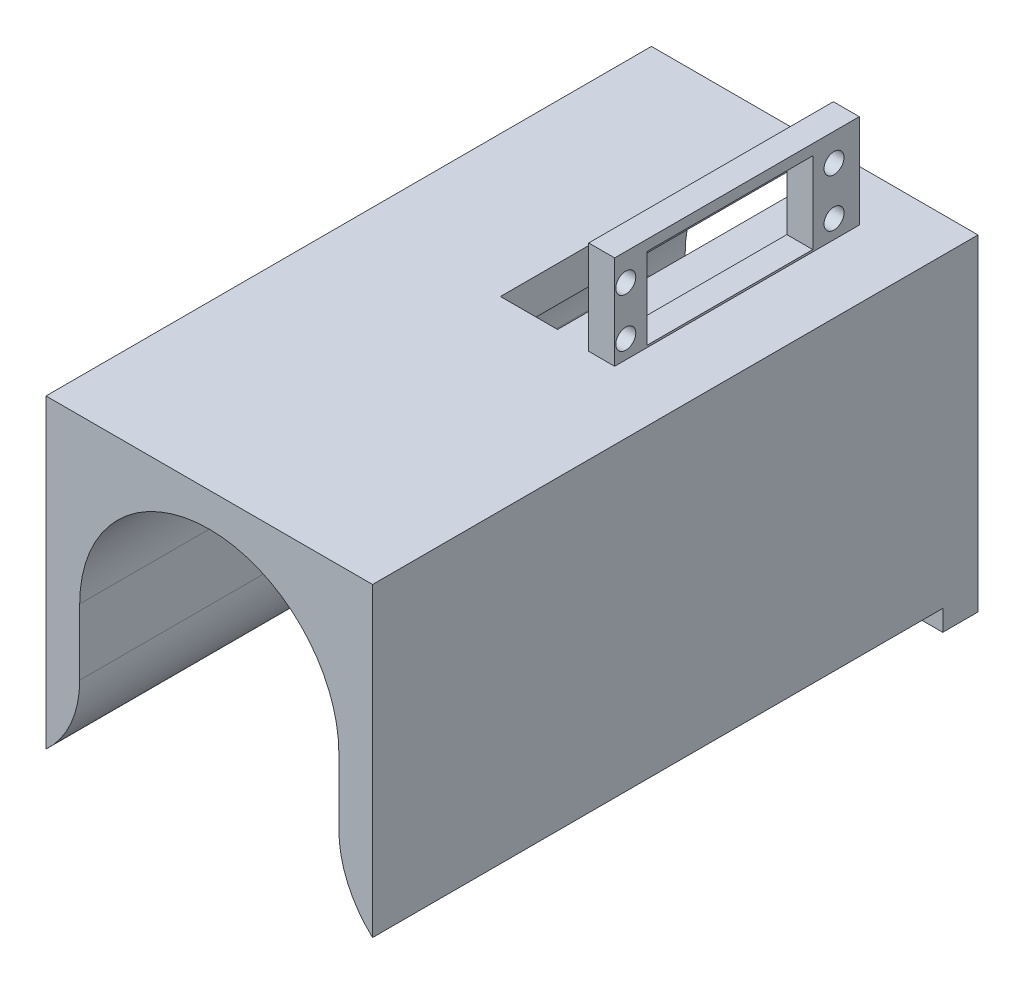
SolidWorks part; units mm, degrees
ref_plane "Front Plane" through (0, 0, 0) normal (0, 0, 1) x (1, 0, 0)
ref_plane "Top Plane" through (0, 0, 0) normal (0, 1, 0) x (1, 0, 0)
ref_plane "Right Plane" through (0, 0, 0) normal (1, 0, 0) x (0, 0, -1)
sketch "Sketch1" plane through (0, 0, 0) normal (0, 0, 1) x (1, 0, 0)
  line L5 (-34.925, -34.925) -> (34.925, 34.925) construction
  line L6 (-34.925, 34.925) -> (34.925, -34.925) construction
  line L7 (-40.005, -40.005) -> (40.005, -40.005)
  line L8 (-40.005, -40.005) -> (-40.005, 40.005)
  line L9 (-40.005, 40.005) -> (40.005, 40.005)
  line L10 (40.005, -40.005) -> (40.005, 40.005)
  line L11 (-40.005, -40.005) -> (40.005, 40.005) construction
  line L12 (-40.005, 40.005) -> (40.005, -40.005) construction
  point P0 (0, 0)
  point P6 (0, 0)
extrude "Boss-Extrude1" add sketch "Sketch1" along normal blind 2.54
sketch "Sketch2" plane through (0, 0, 2.54) normal (0, 0, 1) x (1, 0, 0)
  line L1 (-40.005, 40.005) -> (40.005, 40.005)
  line L2 (-40.005, 40.005) -> (-40.005, -40.005)
  line L3 (-40.005, -40.005) -> (40.005, -40.005)
  line L4 (40.005, 40.005) -> (40.005, -40.005)
  line L5 (-34.925, -34.925) -> (34.925, -34.925)
  line L6 (-34.925, -34.925) -> (-34.925, 34.925)
  line L7 (-34.925, 34.925) -> (34.925, 34.925)
  line L8 (34.925, -34.925) -> (34.925, 34.925)
  line L9 (-34.925, -34.925) -> (34.925, 34.925) construction
  line L10 (-34.925, 34.925) -> (34.925, -34.925) construction
  point P6 (0, 0)
  dimension "D1" = 5.08
  dimension "D2" = 5.08
extrude "Boss-Extrude2" add sketch "Sketch2" along normal blind 145.796
sketch "Sketch3" plane through (0, 0, 0) normal (0, 0, -1) x (-1, 0, 0)
  circle A0 centre (0, 0) radius 31.75
  dimension "D1" = 63.5
extrude "Cut-Extrude1" cut sketch "Sketch3" against normal blind 69.85
sketch "Sketch5" plane through (0, -40.005, 0) normal (0, -1, 0) x (1, 0, 0)
  line L1 (-40.005, 148.336) -> (40.005, 148.336)
  line L2 (-40.005, 148.336) -> (-40.005, 8.636)
  line L3 (-40.005, 8.636) -> (40.005, 8.636)
  line L4 (40.005, 148.336) -> (40.005, 8.636)
  line L5 (-40.005, 148.336) -> (40.005, 8.636) construction
  line L6 (40.005, 148.336) -> (-40.005, 8.636) construction
  point P5 (0, 78.486)
  dimension "D1" = 139.7
extrude "Cut-Extrude3" cut sketch "Sketch5" against normal blind 5.08 contours L3 L1 | L1 region at (0, -40.005, 78.486)
sketch "Sketch6" plane through (0, 0, 2.54) normal (0, 0, 1) x (1, 0, 0)
  line L1 (-34.925, 34.925) -> (34.925, 34.925)
  line L2 (-34.925, 34.925) -> (-34.925, -34.925)
  line L3 (-34.925, -34.925) -> (34.925, -34.925)
  line L4 (34.925, 34.925) -> (34.925, -34.925)
  circle A0 centre (0, 0) radius 31.75
extrude "Boss-Extrude3" add sketch "Sketch6" along normal blind 145.796
sketch "Sketch8" plane through (0, 0, 148.336) normal (0, 0, 1) x (1, 0, 0)
  line L0 (-31.75, 0) -> (-31.75, -34.925)
  line L1 (-40.005, -34.925) -> (40.005, -34.925) construction
  line L2 (31.75, 0) -> (31.75, -34.925)
  line L3 (-40.005, -34.925) -> (40.005, -34.925) construction
  line L4 (31.75, -34.925) -> (-31.75, -34.925)
  line L5 (-31.75, 0) -> (31.75, 0)
  circle A0 centre (0, 0) radius 31.75
  circle A1 centre (0, 0) radius 31.75 construction
  line M3 (-40.005, -34.925) -> (40.005, -34.925)
  circle M9 centre (0, 0) radius 31.75
extrude "Cut-Extrude5" cut sketch "Sketch8" against normal blind 139.7 contours L2 L0 M9 M3 region at (0, -32.4747, 148.336)
fillet "Fillet2" radius 25.4 2 edges at (31.75, -34.925, 78.486) (-31.75, -34.925, 78.486)
sketch "Sketch9" plane through (0, 40.005, 0) normal (0, 1, 0) x (1, 0, 0)
  line L0 (-40.005, -148.336) -> (40.005, 0) construction
  line L7 (23.368, -72.39) -> (17.018, -72.39)
  line L8 (23.368, -72.39) -> (23.368, -12.446)
  line L9 (23.368, -12.446) -> (17.018, -12.446)
  line L10 (17.018, -72.39) -> (17.018, -12.446)
  point P7 (0, -74.168)
  dimension "D1" = 6.35
  dimension "D2" = 59.944
  dimension "D3" = 17.018
extrude "Boss-Extrude5" add sketch "Sketch9" along normal blind 23
sketch "Sketch10" plane through (23.368, 0, 0) normal (1, 0, 0) x (0, 0, -1)
  line L0 (-64.4492, 40.005) -> (-64.4492, 63.005) construction
  line L1 (-64.4492, 40.5026) -> (-23.8492, 40.5026)
  line L2 (-64.4492, 40.5026) -> (-64.4492, 60.4026)
  line L3 (-64.4492, 60.4026) -> (-23.8492, 60.4026)
  line L4 (-23.8492, 40.5026) -> (-23.8492, 60.4026)
  line L5 (-72.39, 40.005) -> (-12.446, 40.005) construction
  line L6 (-72.39, 63.005) -> (-12.446, 63.005) construction
  circle A0 centre (-69.6592, 44.5026) radius 2.45
  circle A1 centre (-69.6592, 56.4026) radius 2.45
  circle A2 centre (-18.6392, 44.5026) radius 2.45
  circle A3 centre (-18.6392, 56.2445) radius 2.45
  dimension "D3" = 4.9
  dimension "D4" = 4.9
  dimension "D5" = 4.9
  dimension "D6" = 4.9
  dimension "D7" = 5.21
  dimension "D8" = 5.21
  dimension "D1" = 40.6
  dimension "D2" = 19.9
  dimension "D9" = 5.21
  dimension "D10" = 5.21
  dimension "D11" = 4
  dimension "D12" = 4
  dimension "D13" = 4
  dimension "D14" = 4.1581
extrude "Cut-Extrude7" cut sketch "Sketch10" against normal blind 23
ref_plane "Plane1" through (23.368, 63.005, 12.446) normal (-1, 0, 0) x (0, 0, 1)
sketch "Sketch12" plane through (0, 40.005, 0) normal (0, 1, 0) x (1, 0, 0)
  line L0 (17.018, -12.446) -> (17.018, -72.39) construction
  line L1 (8.568, -71.5702) -> (-5.432, -71.5702)
  line L2 (8.568, -71.5702) -> (8.568, 0.4298)
  line L3 (8.568, 0.4298) -> (-5.432, 0.4298)
  line L4 (-5.432, -71.5702) -> (-5.432, 0.4298)
  dimension "D1" = 8.45
  dimension "D2" = 72
  dimension "D3" = 14
extrude "Cut-Extrude10" cut sketch "Sketch12" against normal blind 24.13
